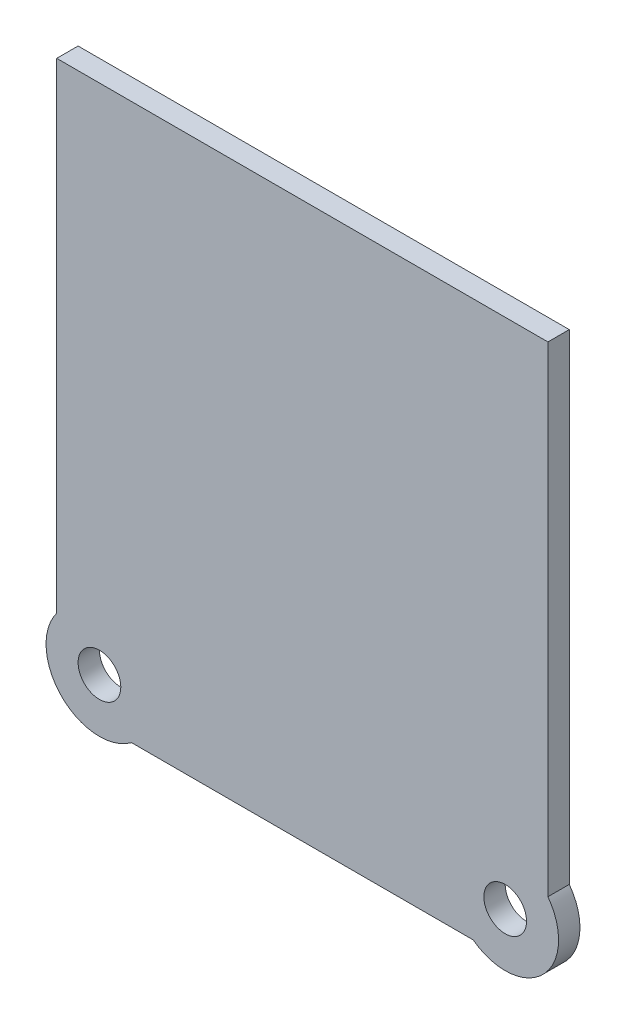
SolidWorks part; units mm, degrees
ref_plane "Front Plane" through (0, 0, 0) normal (0, 0, 1) x (1, 0, 0)
ref_plane "Top Plane" through (0, 0, 0) normal (0, 1, 0) x (1, 0, 0)
ref_plane "Right Plane" through (0, 0, 0) normal (1, 0, 0) x (0, 0, -1)
sketch "Sketch1" plane through (0, 0, 0) normal (0, 0, 1) x (1, 0, 0)
  line L0 (0, 0) -> (0, 152.4) construction
  line L1 (0.0027, -12.7) -> (-50.8, -12.7)
  line L2 (-73.025, 9.525) -> (-73.025, 152.4)
  line L3 (-73.025, 152.4) -> (73.025, 152.4)
  line L4 (73.025, 9.525) -> (73.025, 152.4)
  line L5 (-0.0027, -12.7) -> (50.8, -12.7)
  circle A0 centre (-60.325, 0) radius 6.35
  arc A1 (-73.025, 9.525) -> (-50.8, -12.7) centre (-60.325, 0) ccw
  arc A2 (73.025, 9.525) -> (50.8, -12.7) centre (60.325, 0) cw
  circle A3 centre (60.325, 0) radius 6.35
  dimension "D1" = 12.7
  dimension "D2" = 31.75
  dimension "D3" = 60.325
  dimension "D4" = 146.05
  dimension "D5" = 12.7
  dimension "D6" = 152.4
extrude "Boss-Extrude1" add sketch "Sketch1" along normal mid plane 6.35 contours A2 L4 L3 L2 A1 L1 L5 A0 A3 region at (0, 70.0905, 0)
